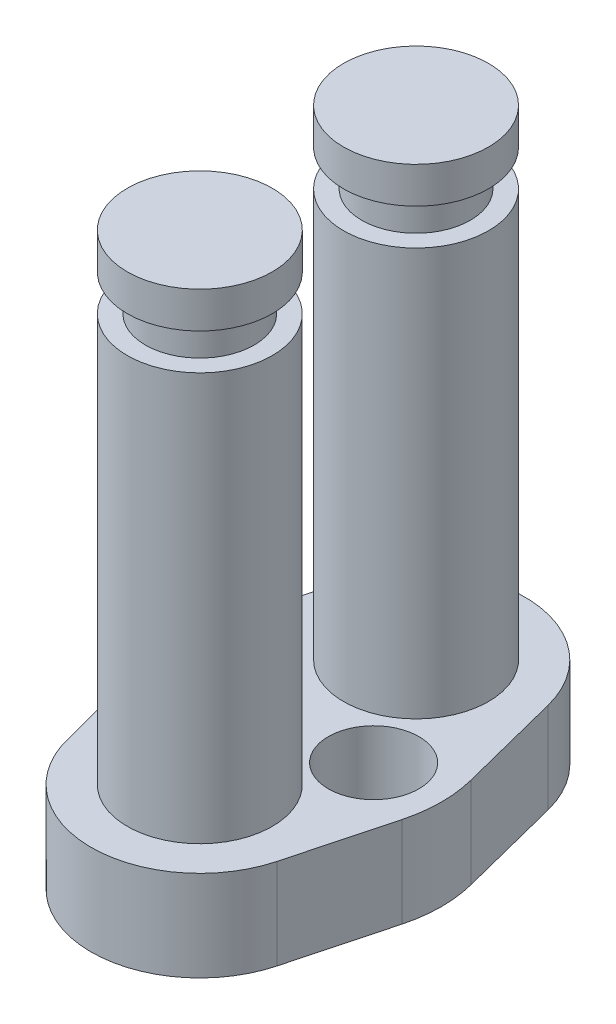
SolidWorks part; units mm, degrees
ref_plane "Front Plane" through (0, 0, 0) normal (0, 0, 1) x (1, 0, 0)
ref_plane "Top Plane" through (0, 0, 0) normal (0, 1, 0) x (1, 0, 0)
ref_plane "Right Plane" through (0, 0, 0) normal (1, 0, 0) x (0, 0, -1)
sketch "Sketch2" plane through (0, 0, 0) normal (0, 1, 0) x (1, 0, 0)
  line L0 (3.75, 7.5) -> (3.75, -7.5) construction
  line L1 (-3.4934, -1.9449) -> (-1.9217, -7.7985)
  line L2 (10.9985, -1.9261) -> (9.5488, -7.3818)
  line L3 (11.0189, 1.8474) -> (9.5651, 7.5676)
  line L4 (-2.0651, 7.5676) -> (-3.5189, 1.8474)
  circle A0 centre (7.5, 0) radius 2.5
  circle A1 centre (0, 0) radius 2.5
  circle A2 centre (3.75, 0) radius 7.5
  circle A3 centre (3.75, 6.0897) radius 4 construction
  circle A4 centre (3.75, -5.841) radius 4 construction
  circle A5 centre (3.75, 6.0897) radius 6
  circle A6 centre (3.75, -5.841) radius 6
  dimension "D1" = 7.5
  dimension "D2" = 5
  dimension "D4" = 15
  dimension "D5" = 12
  dimension "D6" = 12
  dimension "D7" = 8
  dimension "D8" = 8
  dimension "D3" = 3.75
extrude "Boss-Extrude2" add sketch "Sketch2" along normal blind 5 contours A2 A6 A0 A5 A1 | A6 A2 L1 | A6 A2 A5 A0 | A6 L2 A2 | A6 A1 A5 A2 | A6 A2 L1 | A6 A0 A5 | A5 A6 | A6 A5 A1 | A6 A5 A0 A2 A1 | A2 A5 | A5 A2 L3 | A5 L4 A2 region at (-2.5745, 0, 4.6608) region at (-2.5654, 0, -0.0708) region at (3.751, 0, 8.7182) region at (-2.5748, 0, -4.7398) region at (3.75, 0, 4.159) region at (3.75, 0, -8.8393) region at (3.75, 0, -4.2146) region at (10.0654, 0, -0.0708) region at (10.0744, 0, 4.6847) region at (10.0748, 0, -4.7398) region at (2.687, 0, -0.125) region at (4.813, 0, -0.125) region at (3.75, 0, -0.1244)
sketch "Sketch3" plane through (0, 5, 0) normal (0, 1, 0) x (1, 0, 0)
  line L0 (3.75, -11.841) -> (3.75, 12.0897) construction
  line L1 (-3.7498, -0.0504) -> (11.2499, -0.0406) construction
  circle A0 centre (3.75, -5.841) radius 4
  circle A1 centre (3.75, 6.0897) radius 4
  arc A2 (-1.9217, -7.7985) -> (9.5488, -7.3818) centre (3.75, -5.841) ccw construction
  arc A3 (9.5651, 7.5676) -> (-2.0651, 7.5676) centre (3.75, 6.0897) ccw construction
  arc A4 (-3.5189, 1.8474) -> (-3.4934, -1.9449) centre (3.75, 0) ccw construction
  arc A5 (10.9985, -1.9261) -> (11.0189, 1.8474) centre (3.75, 0) ccw construction
  dimension "D1" = 8
extrude "Boss-Extrude3" add sketch "Sketch3" along normal blind 22.5
sketch "Sketch4" plane through (0, 27.5, 0) normal (0, 1, 0) x (1, 0, 0)
  circle A0 centre (3.75, -5.841) radius 3
  circle A1 centre (3.75, 6.0897) radius 3
  circle A2 centre (3.75, -5.841) radius 4 construction
  circle A3 centre (3.75, 6.0897) radius 4 construction
  dimension "D1" = 6
  dimension "D2" = 6
extrude "Boss-Extrude4" add sketch "Sketch4" along normal blind 2
sketch "Sketch5" plane through (0, 29.5, 0) normal (0, 1, 0) x (1, 0, 0)
  circle A0 centre (3.75, -5.841) radius 4
  circle A1 centre (3.75, 6.0897) radius 4
  dimension "D1" = 8
  dimension "D2" = 8
extrude "Boss-Extrude5" add sketch "Sketch5" along normal blind 2
